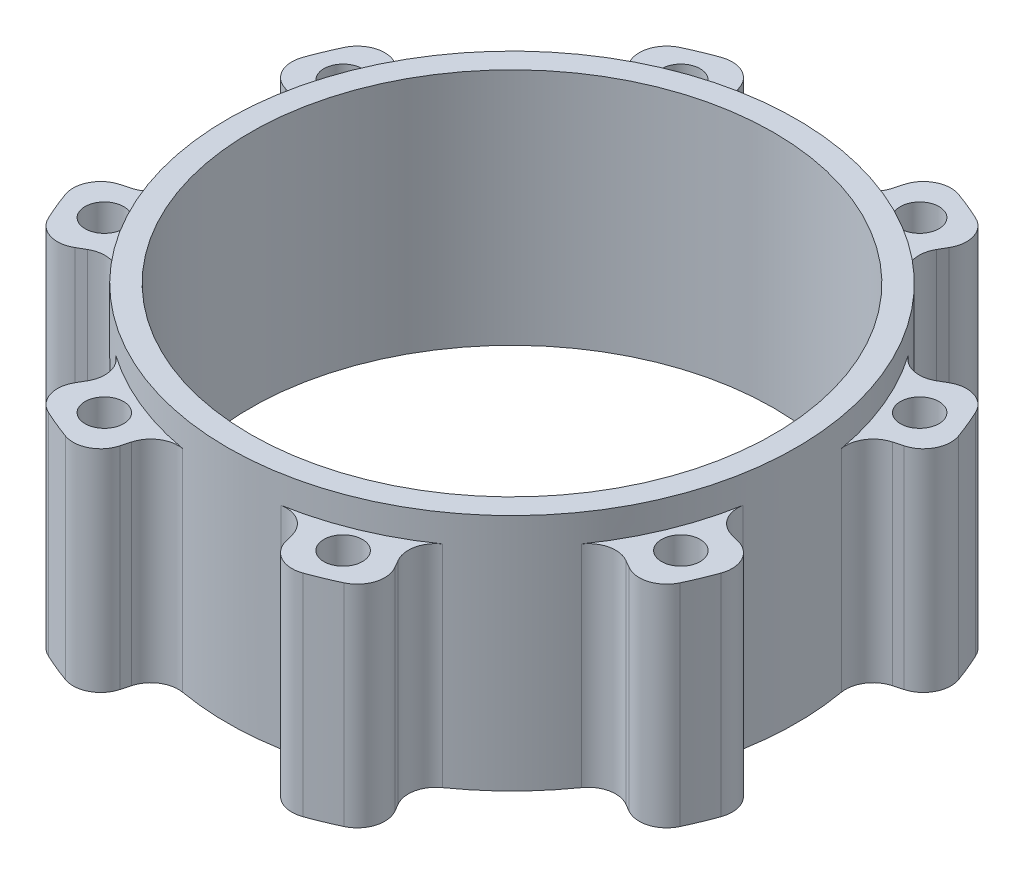
SolidWorks part; units mm, degrees
material "ABS"
ref_plane "前视基准面" through (0, 0, 0) normal (0, 0, 1) x (1, 0, 0)
ref_plane "上视基准面" through (0, 0, 0) normal (0, 1, 0) x (1, 0, 0)
ref_plane "右视基准面" through (0, 0, 0) normal (1, 0, 0) x (0, 0, -1)
other "Configuration Table"
sketch "草图1" plane through (0, 0, 0) normal (0, 1, 0) x (1, 0, 0)
  circle A0 centre (0, 0) radius 34 construction
  circle A1 centre (0, 0) radius 28.5
  circle A2 centre (0, 0) radius 38
  dimension "D1" = 68
  dimension "D2" = 4
  dimension "D3" = 57
extrude "凸台-拉伸1" add sketch "草图1" along normal blind 12
sketch "草图2" plane through (0, 12, 0) normal (0, 1, 0) x (1, 0, 0)
  line L0 (0, 0) -> (13.0112, 31.4119) construction
  circle A0 centre (0, 0) radius 34 construction
  circle A1 centre (13.0112, 31.4119) radius 2.1
  circle A2 centre (31.4119, 13.0112) radius 2.1
  circle A3 centre (31.4119, -13.0112) radius 2.1
  circle A4 centre (13.0112, -31.4119) radius 2.1
  circle A5 centre (-13.0112, -31.4119) radius 2.1
  circle A6 centre (-31.4119, -13.0112) radius 2.1
  circle A7 centre (-31.4119, 13.0112) radius 2.1
  circle A8 centre (-13.0112, 31.4119) radius 2.1
  dimension "D1" = 68
  dimension "D2" = 4.2
  dimension "D4" = 34
  dimension "D3" = 8
extrude "切除-拉伸1" cut sketch "草图2" against normal through all
sketch "草图4" plane through (0, 12, 0) normal (0, 1, 0) x (1, 0, 0)
  circle A0 centre (0, 0) radius 31
  circle A1 centre (0, 0) radius 28.5 construction
  circle A2 centre (0, 0) radius 28.5
  dimension "D1" = 62
extrude "凸台-拉伸2" add sketch "草图4" along normal blind 3
sketch "草图5" plane through (0, 0, 0) normal (0, -1, 0) x (1, 0, 0)
  line L0 (-9.8351, 36.7052) -> (0, 0)
  line L1 (0, 0) -> (9.8351, 36.7052)
  line L2 (0, 0) -> (0, 38) construction
  line L3 (0, 0) -> (32.909, 19)
  line L4 (19, 32.909) -> (0, 0)
  line L5 (0, 0) -> (36.7052, -9.8351)
  line L6 (36.7052, 9.8351) -> (0, 0)
  line L7 (0, 0) -> (19, -32.909)
  line L8 (32.909, -19) -> (0, 0)
  line L9 (0, 0) -> (-9.8351, -36.7052)
  line L10 (9.8351, -36.7052) -> (0, 0)
  line L11 (0, 0) -> (-32.909, -19)
  line L12 (-19, -32.909) -> (0, 0)
  line L13 (0, 0) -> (-36.7052, 9.8351)
  line L14 (-36.7052, -9.8351) -> (0, 0)
  line L15 (0, 0) -> (-19, 32.909)
  line L16 (-32.909, 19) -> (0, 0)
  circle A0 centre (0, 0) radius 31
  circle A1 centre (0, 0) radius 38 construction
  point P25 (0, 0)
  circle M12 centre (0, 0) radius 38
  dimension "D1" = 62
  dimension "D2" = 15
  dimension "D3" = 15
  dimension "D4" = 8
extrude "切除-拉伸2" cut sketch "草图5" against normal through all contours A0 L5 L6 M12 | A0 L3 L4 M12 | A0 L2 L0 M12 | L2 A0 L1 M12 | A0 L15 L16 M12 | A0 L13 L14 M12 | A0 L11 L12 M12 | A0 L9 L10 M12 | A0 L7 L8 M12 region at (-4.5057, 0, 34.2243) region at (4.5057, 0, 34.2243) region at (-24.2002, 0, 24.2002) region at (24.2002, 0, 24.2002) region at (34.2243, 0, 0) region at (24.2002, 0, -24.2002) region at (0, 0, -34.2243) region at (-24.2002, 0, -24.2002) region at (-34.2243, 0, 0)
fillet "圆角1" radius 3 32 edges at (15.5, 6, -26.8468) (19, 6, -32.909) (9.8351, 6, -36.7052) (8.0234, 6, -29.9437) (-8.0234, 6, -29.9437) (-9.8351, 6, -36.7052) (-19, 6, -32.909) (-15.5, 6, -26.8468) (-26.8468, 6, -15.5) (-32.909, 6, -19) (-36.7052, 6, -9.8351) (-29.9437, 6, -8.0234) (-29.9437, 6, 8.0234) (-36.7052, 6, 9.8351) (-32.909, 6, 19) (-26.8468, 6, 15.5) (-15.5, 6, 26.8468) (-19, 6, 32.909) (-9.8351, 6, 36.7052) (-8.0234, 6, 29.9437) (8.0234, 6, 29.9437) (9.8351, 6, 36.7052) (15.5, 6, 26.8468) (26.8468, 6, 15.5) (32.909, 6, 19) (36.7052, 6, 9.8351) (29.9437, 6, 8.0234) (29.9437, 6, -8.0234) (36.7052, 6, -9.8351) (32.909, 6, -19) (26.8468, 6, -15.5) (19, 6, 32.909)
sketch "草图6" plane through (0, 12, 0) normal (0, 1, 0) x (1, 0, 0)
  line L0 (-16.9337, -29.33) -> (-17.4356, -30.1993) construction
  line L1 (-9.0253, -33.683) -> (-8.7655, -32.7134) construction
  line L2 (-32.7134, -8.7655) -> (-33.683, -9.0253) construction
  line L3 (-30.1993, -17.4356) -> (-29.33, -16.9337) construction
  line L4 (-29.33, 16.9337) -> (-30.1993, 17.4356) construction
  line L5 (-33.683, 9.0253) -> (-32.7134, 8.7655) construction
  line L6 (-8.7655, 32.7134) -> (-9.0253, 33.683) construction
  line L7 (-17.4356, 30.1993) -> (-16.9337, 29.33) construction
  line L8 (16.9337, 29.33) -> (17.4356, 30.1993) construction
  line L9 (9.0253, 33.683) -> (8.7655, 32.7134) construction
  line L10 (32.7134, 8.7655) -> (33.683, 9.0253) construction
  line L11 (30.1993, 17.4356) -> (29.33, 16.9337) construction
  line L12 (8.7655, -32.7134) -> (9.0253, -33.683) construction
  line L13 (17.4356, -30.1993) -> (16.9337, -29.33) construction
  line L14 (29.33, -16.9337) -> (30.1993, -17.4356) construction
  line L15 (33.683, -9.0253) -> (32.7134, -8.7655) construction
  line L16 (-16.9337, -29.33) -> (-17.4356, -30.1993)
  line L17 (-9.0253, -33.683) -> (-8.7655, -32.7134)
  line L18 (-32.7134, -8.7655) -> (-33.683, -9.0253)
  line L19 (-30.1993, -17.4356) -> (-29.33, -16.9337)
  line L20 (-29.33, 16.9337) -> (-30.1993, 17.4356)
  line L21 (-33.683, 9.0253) -> (-32.7134, 8.7655)
  line L22 (-8.7655, 32.7134) -> (-9.0253, 33.683)
  line L23 (-17.4356, 30.1993) -> (-16.9337, 29.33)
  line L24 (16.9337, 29.33) -> (17.4356, 30.1993)
  line L25 (9.0253, 33.683) -> (8.7655, 32.7134)
  line L26 (32.7134, 8.7655) -> (33.683, 9.0253)
  line L27 (30.1993, 17.4356) -> (29.33, 16.9337)
  line L28 (8.7655, -32.7134) -> (9.0253, -33.683)
  line L29 (17.4356, -30.1993) -> (16.9337, -29.33)
  line L30 (29.33, -16.9337) -> (30.1993, -17.4356)
  line L31 (33.683, -9.0253) -> (32.7134, -8.7655)
  arc A0 (-17.4356, -30.1993) -> (-16.1093, -34.4164) centre (-14.8375, -31.6993) ccw construction
  arc A1 (-16.1093, -34.4164) -> (-12.9451, -35.7271) centre (0, 0) ccw construction
  arc A2 (-12.9451, -35.7271) -> (-9.0253, -33.683) centre (-11.9231, -32.9065) ccw construction
  arc A3 (-5.35, -30.5349) -> (-8.7655, -32.7134) centre (-5.8677, -33.4898) ccw construction
  arc A4 (-17.8084, -25.3744) -> (-5.35, -30.5349) centre (0, 0) ccw construction
  arc A5 (-16.9337, -29.33) -> (-17.8084, -25.3744) centre (-19.5318, -27.83) ccw construction
  arc A6 (-33.683, -9.0253) -> (-35.7271, -12.9451) centre (-32.9065, -11.9231) ccw construction
  arc A7 (-35.7271, -12.9451) -> (-34.4164, -16.1093) centre (0, 0) ccw construction
  arc A8 (-34.4164, -16.1093) -> (-30.1993, -17.4356) centre (-31.6993, -14.8375) ccw construction
  arc A9 (-25.3744, -17.8084) -> (-29.33, -16.9337) centre (-27.83, -19.5318) ccw construction
  arc A10 (-30.5349, -5.35) -> (-25.3744, -17.8084) centre (0, 0) ccw construction
  arc A11 (-32.7134, -8.7655) -> (-30.5349, -5.35) centre (-33.4898, -5.8677) ccw construction
  arc A12 (-30.1993, 17.4356) -> (-34.4164, 16.1093) centre (-31.6993, 14.8375) ccw construction
  arc A13 (-34.4164, 16.1093) -> (-35.7271, 12.9451) centre (0, 0) ccw construction
  arc A14 (-35.7271, 12.9451) -> (-33.683, 9.0253) centre (-32.9065, 11.9231) ccw construction
  arc A15 (-30.5349, 5.35) -> (-32.7134, 8.7655) centre (-33.4898, 5.8677) ccw construction
  arc A16 (-25.3744, 17.8084) -> (-30.5349, 5.35) centre (0, 0) ccw construction
  arc A17 (-29.33, 16.9337) -> (-25.3744, 17.8084) centre (-27.83, 19.5318) ccw construction
  arc A18 (-9.0253, 33.683) -> (-12.9451, 35.7271) centre (-11.9231, 32.9065) ccw construction
  arc A19 (-12.9451, 35.7271) -> (-16.1093, 34.4164) centre (0, 0) ccw construction
  arc A20 (-16.1093, 34.4164) -> (-17.4356, 30.1993) centre (-14.8375, 31.6993) ccw construction
  arc A21 (-17.8084, 25.3744) -> (-16.9337, 29.33) centre (-19.5318, 27.83) ccw construction
  arc A22 (-5.35, 30.5349) -> (-17.8084, 25.3744) centre (0, 0) ccw construction
  arc A23 (-8.7655, 32.7134) -> (-5.35, 30.5349) centre (-5.8677, 33.4898) ccw construction
  arc A24 (17.4356, 30.1993) -> (16.1093, 34.4164) centre (14.8375, 31.6993) ccw construction
  arc A25 (16.1093, 34.4164) -> (12.9451, 35.7271) centre (0, 0) ccw construction
  arc A26 (12.9451, 35.7271) -> (9.0253, 33.683) centre (11.9231, 32.9065) ccw construction
  arc A27 (5.35, 30.5349) -> (8.7655, 32.7134) centre (5.8677, 33.4898) ccw construction
  arc A28 (17.8084, 25.3744) -> (5.35, 30.5349) centre (0, 0) ccw construction
  arc A29 (16.9337, 29.33) -> (17.8084, 25.3744) centre (19.5318, 27.83) ccw construction
  arc A30 (33.683, 9.0253) -> (35.7271, 12.9451) centre (32.9065, 11.9231) ccw construction
  arc A31 (35.7271, 12.9451) -> (34.4164, 16.1093) centre (0, 0) ccw construction
  arc A32 (34.4164, 16.1093) -> (30.1993, 17.4356) centre (31.6993, 14.8375) ccw construction
  arc A33 (25.3744, 17.8084) -> (29.33, 16.9337) centre (27.83, 19.5318) ccw construction
  arc A34 (30.5349, 5.35) -> (25.3744, 17.8084) centre (0, 0) ccw construction
  arc A35 (32.7134, 8.7655) -> (30.5349, 5.35) centre (33.4898, 5.8677) ccw construction
  arc A36 (9.0253, -33.683) -> (12.9451, -35.7271) centre (11.9231, -32.9065) ccw construction
  arc A37 (12.9451, -35.7271) -> (16.1093, -34.4164) centre (0, 0) ccw construction
  arc A38 (16.1093, -34.4164) -> (17.4356, -30.1993) centre (14.8375, -31.6993) ccw construction
  arc A39 (17.8084, -25.3744) -> (16.9337, -29.33) centre (19.5318, -27.83) ccw construction
  arc A40 (5.35, -30.5349) -> (17.8084, -25.3744) centre (0, 0) ccw construction
  arc A41 (8.7655, -32.7134) -> (5.35, -30.5349) centre (5.8677, -33.4898) ccw construction
  arc A42 (30.1993, -17.4356) -> (34.4164, -16.1093) centre (31.6993, -14.8375) ccw construction
  arc A43 (34.4164, -16.1093) -> (35.7271, -12.9451) centre (0, 0) ccw construction
  arc A44 (35.7271, -12.9451) -> (33.683, -9.0253) centre (32.9065, -11.9231) ccw construction
  arc A45 (30.5349, -5.35) -> (32.7134, -8.7655) centre (33.4898, -5.8677) ccw construction
  arc A46 (25.3744, -17.8084) -> (30.5349, -5.35) centre (0, 0) ccw construction
  arc A47 (29.33, -16.9337) -> (25.3744, -17.8084) centre (27.83, -19.5318) ccw construction
  arc A48 (-17.4356, -30.1993) -> (-16.1093, -34.4164) centre (-14.8375, -31.6993) ccw
  arc A49 (-16.1093, -34.4164) -> (-12.9451, -35.7271) centre (0, 0) ccw
  arc A50 (-12.9451, -35.7271) -> (-9.0253, -33.683) centre (-11.9231, -32.9065) ccw
  arc A51 (-5.35, -30.5349) -> (-8.7655, -32.7134) centre (-5.8677, -33.4898) ccw
  arc A52 (-17.8084, -25.3744) -> (-5.35, -30.5349) centre (0, 0) ccw
  arc A53 (-16.9337, -29.33) -> (-17.8084, -25.3744) centre (-19.5318, -27.83) ccw
  arc A54 (-33.683, -9.0253) -> (-35.7271, -12.9451) centre (-32.9065, -11.9231) ccw
  arc A55 (-35.7271, -12.9451) -> (-34.4164, -16.1093) centre (0, 0) ccw
  arc A56 (-34.4164, -16.1093) -> (-30.1993, -17.4356) centre (-31.6993, -14.8375) ccw
  arc A57 (-25.3744, -17.8084) -> (-29.33, -16.9337) centre (-27.83, -19.5318) ccw
  arc A58 (-30.5349, -5.35) -> (-25.3744, -17.8084) centre (0, 0) ccw
  arc A59 (-32.7134, -8.7655) -> (-30.5349, -5.35) centre (-33.4898, -5.8677) ccw
  arc A60 (-30.1993, 17.4356) -> (-34.4164, 16.1093) centre (-31.6993, 14.8375) ccw
  arc A61 (-34.4164, 16.1093) -> (-35.7271, 12.9451) centre (0, 0) ccw
  arc A62 (-35.7271, 12.9451) -> (-33.683, 9.0253) centre (-32.9065, 11.9231) ccw
  arc A63 (-30.5349, 5.35) -> (-32.7134, 8.7655) centre (-33.4898, 5.8677) ccw
  arc A64 (-25.3744, 17.8084) -> (-30.5349, 5.35) centre (0, 0) ccw
  arc A65 (-29.33, 16.9337) -> (-25.3744, 17.8084) centre (-27.83, 19.5318) ccw
  arc A66 (-9.0253, 33.683) -> (-12.9451, 35.7271) centre (-11.9231, 32.9065) ccw
  arc A67 (-12.9451, 35.7271) -> (-16.1093, 34.4164) centre (0, 0) ccw
  arc A68 (-16.1093, 34.4164) -> (-17.4356, 30.1993) centre (-14.8375, 31.6993) ccw
  arc A69 (-17.8084, 25.3744) -> (-16.9337, 29.33) centre (-19.5318, 27.83) ccw
  arc A70 (-5.35, 30.5349) -> (-17.8084, 25.3744) centre (0, 0) ccw
  arc A71 (-8.7655, 32.7134) -> (-5.35, 30.5349) centre (-5.8677, 33.4898) ccw
  arc A72 (17.4356, 30.1993) -> (16.1093, 34.4164) centre (14.8375, 31.6993) ccw
  arc A73 (16.1093, 34.4164) -> (12.9451, 35.7271) centre (0, 0) ccw
  arc A74 (12.9451, 35.7271) -> (9.0253, 33.683) centre (11.9231, 32.9065) ccw
  arc A75 (5.35, 30.5349) -> (8.7655, 32.7134) centre (5.8677, 33.4898) ccw
  arc A76 (17.8084, 25.3744) -> (5.35, 30.5349) centre (0, 0) ccw
  arc A77 (16.9337, 29.33) -> (17.8084, 25.3744) centre (19.5318, 27.83) ccw
  arc A78 (33.683, 9.0253) -> (35.7271, 12.9451) centre (32.9065, 11.9231) ccw
  arc A79 (35.7271, 12.9451) -> (34.4164, 16.1093) centre (0, 0) ccw
  arc A80 (34.4164, 16.1093) -> (30.1993, 17.4356) centre (31.6993, 14.8375) ccw
  arc A81 (25.3744, 17.8084) -> (29.33, 16.9337) centre (27.83, 19.5318) ccw
  arc A82 (30.5349, 5.35) -> (25.3744, 17.8084) centre (0, 0) ccw
  arc A83 (32.7134, 8.7655) -> (30.5349, 5.35) centre (33.4898, 5.8677) ccw
  arc A84 (9.0253, -33.683) -> (12.9451, -35.7271) centre (11.9231, -32.9065) ccw
  arc A85 (12.9451, -35.7271) -> (16.1093, -34.4164) centre (0, 0) ccw
  arc A86 (16.1093, -34.4164) -> (17.4356, -30.1993) centre (14.8375, -31.6993) ccw
  arc A87 (17.8084, -25.3744) -> (16.9337, -29.33) centre (19.5318, -27.83) ccw
  arc A88 (5.35, -30.5349) -> (17.8084, -25.3744) centre (0, 0) ccw
  arc A89 (8.7655, -32.7134) -> (5.35, -30.5349) centre (5.8677, -33.4898) ccw
  arc A90 (30.1993, -17.4356) -> (34.4164, -16.1093) centre (31.6993, -14.8375) ccw
  arc A91 (34.4164, -16.1093) -> (35.7271, -12.9451) centre (0, 0) ccw
  arc A92 (35.7271, -12.9451) -> (33.683, -9.0253) centre (32.9065, -11.9231) ccw
  arc A93 (30.5349, -5.35) -> (32.7134, -8.7655) centre (33.4898, -5.8677) ccw
  arc A94 (25.3744, -17.8084) -> (30.5349, -5.35) centre (0, 0) ccw
  arc A95 (29.33, -16.9337) -> (25.3744, -17.8084) centre (27.83, -19.5318) ccw
extrude "凸台-拉伸3" add sketch "草图6" along normal blind 11
sketch "草图7" plane through (0, 15, 0) normal (0, 1, 0) x (1, 0, 0)
  circle A0 centre (0, 0) radius 28.5 construction
  circle A1 centre (0, 0) radius 28.5
  arc A16 (5.35, -30.5349) -> (17.8084, -25.3744) centre (0, 0) ccw
  arc A17 (17.8084, -25.3744) -> (25.3744, -17.8084) centre (0, 0) ccw
  arc A18 (25.3744, -17.8084) -> (30.5349, -5.35) centre (0, 0) ccw
  arc A19 (30.5349, -5.35) -> (30.5349, 5.35) centre (0, 0) ccw
  arc A20 (30.5349, 5.35) -> (25.3744, 17.8084) centre (0, 0) ccw
  arc A21 (25.3744, 17.8084) -> (17.8084, 25.3744) centre (0, 0) ccw
  arc A22 (17.8084, 25.3744) -> (5.35, 30.5349) centre (0, 0) ccw
  arc A23 (5.35, 30.5349) -> (-5.35, 30.5349) centre (0, 0) ccw
  arc A24 (-5.35, 30.5349) -> (-17.8084, 25.3744) centre (0, 0) ccw
  arc A25 (-17.8084, 25.3744) -> (-25.3744, 17.8084) centre (0, 0) ccw
  arc A26 (-25.3744, 17.8084) -> (-30.5349, 5.35) centre (0, 0) ccw
  arc A27 (-30.5349, 5.35) -> (-30.5349, -5.35) centre (0, 0) ccw
  arc A28 (-30.5349, -5.35) -> (-25.3744, -17.8084) centre (0, 0) ccw
  arc A29 (-25.3744, -17.8084) -> (-17.8084, -25.3744) centre (0, 0) ccw
  arc A30 (-17.8084, -25.3744) -> (-5.35, -30.5349) centre (0, 0) ccw
  arc A31 (-5.35, -30.5349) -> (5.35, -30.5349) centre (0, 0) ccw
  arc A32 (5.35, -30.5349) -> (17.8084, -25.3744) centre (0, 0) ccw
  arc A33 (17.8084, -25.3744) -> (25.3744, -17.8084) centre (0, 0) ccw
  arc A34 (25.3744, -17.8084) -> (30.5349, -5.35) centre (0, 0) ccw
  arc A35 (30.5349, -5.35) -> (30.5349, 5.35) centre (0, 0) ccw
  arc A36 (30.5349, 5.35) -> (25.3744, 17.8084) centre (0, 0) ccw
  arc A37 (25.3744, 17.8084) -> (17.8084, 25.3744) centre (0, 0) ccw
  arc A38 (17.8084, 25.3744) -> (5.35, 30.5349) centre (0, 0) ccw
  arc A39 (5.35, 30.5349) -> (-5.35, 30.5349) centre (0, 0) ccw
  arc A40 (-5.35, 30.5349) -> (-17.8084, 25.3744) centre (0, 0) ccw
  arc A41 (-17.8084, 25.3744) -> (-25.3744, 17.8084) centre (0, 0) ccw
  arc A42 (-25.3744, 17.8084) -> (-30.5349, 5.35) centre (0, 0) ccw
  arc A43 (-30.5349, 5.35) -> (-30.5349, -5.35) centre (0, 0) ccw
  arc A44 (-30.5349, -5.35) -> (-25.3744, -17.8084) centre (0, 0) ccw
  arc A45 (-25.3744, -17.8084) -> (-17.8084, -25.3744) centre (0, 0) ccw
  arc A46 (-17.8084, -25.3744) -> (-5.35, -30.5349) centre (0, 0) ccw
  arc A47 (-5.35, -30.5349) -> (5.35, -30.5349) centre (0, 0) ccw
  dimension "D1" = 0
extrude "凸台-拉伸4" add sketch "草图7" along normal blind 11
sketch "草图8" plane through (0, 0, 0) normal (0, -1, 0) x (1, 0, 0)
  line L16 (17.4356, -30.1993) -> (16.9337, -29.33)
  line L17 (29.33, -16.9337) -> (30.1993, -17.4356)
  line L18 (33.683, -9.0253) -> (32.7134, -8.7655)
  line L19 (32.7134, 8.7655) -> (33.683, 9.0253)
  line L20 (30.1993, 17.4356) -> (29.33, 16.9337)
  line L21 (16.9337, 29.33) -> (17.4356, 30.1993)
  line L22 (9.0253, 33.683) -> (8.7655, 32.7134)
  line L23 (-8.7655, 32.7134) -> (-9.0253, 33.683)
  line L24 (-17.4356, 30.1993) -> (-16.9337, 29.33)
  line L25 (-29.33, 16.9337) -> (-30.1993, 17.4356)
  line L26 (-33.683, 9.0253) -> (-32.7134, 8.7655)
  line L27 (-32.7134, -8.7655) -> (-33.683, -9.0253)
  line L28 (-30.1993, -17.4356) -> (-29.33, -16.9337)
  line L29 (-16.9337, -29.33) -> (-17.4356, -30.1993)
  line L30 (-9.0253, -33.683) -> (-8.7655, -32.7134)
  line L31 (8.7655, -32.7134) -> (9.0253, -33.683)
  line L32 (17.4356, -30.1993) -> (16.9337, -29.33)
  line L33 (29.33, -16.9337) -> (30.1993, -17.4356)
  line L34 (33.683, -9.0253) -> (32.7134, -8.7655)
  line L35 (32.7134, 8.7655) -> (33.683, 9.0253)
  line L36 (30.1993, 17.4356) -> (29.33, 16.9337)
  line L37 (16.9337, 29.33) -> (17.4356, 30.1993)
  line L38 (9.0253, 33.683) -> (8.7655, 32.7134)
  line L39 (-8.7655, 32.7134) -> (-9.0253, 33.683)
  line L40 (-17.4356, 30.1993) -> (-16.9337, 29.33)
  line L41 (-29.33, 16.9337) -> (-30.1993, 17.4356)
  line L42 (-33.683, 9.0253) -> (-32.7134, 8.7655)
  line L43 (-32.7134, -8.7655) -> (-33.683, -9.0253)
  line L44 (-30.1993, -17.4356) -> (-29.33, -16.9337)
  line L45 (-16.9337, -29.33) -> (-17.4356, -30.1993)
  line L46 (-9.0253, -33.683) -> (-8.7655, -32.7134)
  line L47 (8.7655, -32.7134) -> (9.0253, -33.683)
  circle A0 centre (13.0112, -31.4119) radius 2.1 construction
  circle A1 centre (-31.4119, 13.0112) radius 2.1
  circle A2 centre (-31.4119, 13.0112) radius 2.1
  circle A5 centre (31.4119, -13.0112) radius 2.1 construction
  circle A6 centre (31.4119, 13.0112) radius 2.1 construction
  circle A7 centre (13.0112, 31.4119) radius 2.1 construction
  circle A8 centre (-13.0112, 31.4119) radius 2.1 construction
  circle A9 centre (-31.4119, -13.0112) radius 2.1 construction
  circle A10 centre (-13.0112, -31.4119) radius 2.1 construction
  circle A11 centre (13.0112, -31.4119) radius 2.1
  circle A12 centre (31.4119, -13.0112) radius 2.1
  circle A13 centre (31.4119, 13.0112) radius 2.1
  circle A14 centre (13.0112, 31.4119) radius 2.1
  circle A15 centre (-13.0112, 31.4119) radius 2.1
  circle A16 centre (-31.4119, -13.0112) radius 2.1
  circle A17 centre (-13.0112, -31.4119) radius 2.1
  arc A48 (12.9451, -35.7271) -> (16.1093, -34.4164) centre (0, 0) ccw
  arc A49 (16.1093, -34.4164) -> (17.4356, -30.1993) centre (14.8375, -31.6993) ccw
  arc A50 (17.8084, -25.3744) -> (16.9337, -29.33) centre (19.5318, -27.83) ccw
  arc A51 (17.8084, -25.3744) -> (25.3744, -17.8084) centre (0, 0) ccw
  arc A52 (29.33, -16.9337) -> (25.3744, -17.8084) centre (27.83, -19.5318) ccw
  arc A53 (30.1993, -17.4356) -> (34.4164, -16.1093) centre (31.6993, -14.8375) ccw
  arc A54 (34.4164, -16.1093) -> (35.7271, -12.9451) centre (0, 0) ccw
  arc A55 (35.7271, -12.9451) -> (33.683, -9.0253) centre (32.9065, -11.9231) ccw
  arc A56 (30.5349, -5.35) -> (32.7134, -8.7655) centre (33.4898, -5.8677) ccw
  arc A57 (30.5349, -5.35) -> (30.5349, 5.35) centre (0, 0) ccw
  arc A58 (32.7134, 8.7655) -> (30.5349, 5.35) centre (33.4898, 5.8677) ccw
  arc A59 (33.683, 9.0253) -> (35.7271, 12.9451) centre (32.9065, 11.9231) ccw
  arc A60 (35.7271, 12.9451) -> (34.4164, 16.1093) centre (0, 0) ccw
  arc A61 (34.4164, 16.1093) -> (30.1993, 17.4356) centre (31.6993, 14.8375) ccw
  arc A62 (25.3744, 17.8084) -> (29.33, 16.9337) centre (27.83, 19.5318) ccw
  arc A63 (25.3744, 17.8084) -> (17.8084, 25.3744) centre (0, 0) ccw
  arc A64 (16.9337, 29.33) -> (17.8084, 25.3744) centre (19.5318, 27.83) ccw
  arc A65 (17.4356, 30.1993) -> (16.1093, 34.4164) centre (14.8375, 31.6993) ccw
  arc A66 (16.1093, 34.4164) -> (12.9451, 35.7271) centre (0, 0) ccw
  arc A67 (12.9451, 35.7271) -> (9.0253, 33.683) centre (11.9231, 32.9065) ccw
  arc A68 (5.35, 30.5349) -> (8.7655, 32.7134) centre (5.8677, 33.4898) ccw
  arc A69 (5.35, 30.5349) -> (-5.35, 30.5349) centre (0, 0) ccw
  arc A70 (-8.7655, 32.7134) -> (-5.35, 30.5349) centre (-5.8677, 33.4898) ccw
  arc A71 (-9.0253, 33.683) -> (-12.9451, 35.7271) centre (-11.9231, 32.9065) ccw
  arc A72 (-12.9451, 35.7271) -> (-16.1093, 34.4164) centre (0, 0) ccw
  arc A73 (-16.1093, 34.4164) -> (-17.4356, 30.1993) centre (-14.8375, 31.6993) ccw
  arc A74 (-17.8084, 25.3744) -> (-16.9337, 29.33) centre (-19.5318, 27.83) ccw
  arc A75 (-17.8084, 25.3744) -> (-25.3744, 17.8084) centre (0, 0) ccw
  arc A76 (-29.33, 16.9337) -> (-25.3744, 17.8084) centre (-27.83, 19.5318) ccw
  arc A77 (-30.1993, 17.4356) -> (-34.4164, 16.1093) centre (-31.6993, 14.8375) ccw
  arc A78 (-34.4164, 16.1093) -> (-35.7271, 12.9451) centre (0, 0) ccw
  arc A79 (-35.7271, 12.9451) -> (-33.683, 9.0253) centre (-32.9065, 11.9231) ccw
  arc A80 (-30.5349, 5.35) -> (-32.7134, 8.7655) centre (-33.4898, 5.8677) ccw
  arc A81 (-30.5349, 5.35) -> (-30.5349, -5.35) centre (0, 0) ccw
  arc A82 (-32.7134, -8.7655) -> (-30.5349, -5.35) centre (-33.4898, -5.8677) ccw
  arc A83 (-33.683, -9.0253) -> (-35.7271, -12.9451) centre (-32.9065, -11.9231) ccw
  arc A84 (-35.7271, -12.9451) -> (-34.4164, -16.1093) centre (0, 0) ccw
  arc A85 (-34.4164, -16.1093) -> (-30.1993, -17.4356) centre (-31.6993, -14.8375) ccw
  arc A86 (-25.3744, -17.8084) -> (-29.33, -16.9337) centre (-27.83, -19.5318) ccw
  arc A87 (-25.3744, -17.8084) -> (-17.8084, -25.3744) centre (0, 0) ccw
  arc A88 (-16.9337, -29.33) -> (-17.8084, -25.3744) centre (-19.5318, -27.83) ccw
  arc A89 (-17.4356, -30.1993) -> (-16.1093, -34.4164) centre (-14.8375, -31.6993) ccw
  arc A90 (-16.1093, -34.4164) -> (-12.9451, -35.7271) centre (0, 0) ccw
  arc A91 (-12.9451, -35.7271) -> (-9.0253, -33.683) centre (-11.9231, -32.9065) ccw
  arc A92 (-5.35, -30.5349) -> (-8.7655, -32.7134) centre (-5.8677, -33.4898) ccw
  arc A93 (-5.35, -30.5349) -> (5.35, -30.5349) centre (0, 0) ccw
  arc A94 (8.7655, -32.7134) -> (5.35, -30.5349) centre (5.8677, -33.4898) ccw
  arc A95 (9.0253, -33.683) -> (12.9451, -35.7271) centre (11.9231, -32.9065) ccw
  arc A96 (12.9451, -35.7271) -> (16.1093, -34.4164) centre (0, 0) ccw
  arc A97 (16.1093, -34.4164) -> (17.4356, -30.1993) centre (14.8375, -31.6993) ccw
  arc A98 (17.8084, -25.3744) -> (16.9337, -29.33) centre (19.5318, -27.83) ccw
  arc A99 (17.8084, -25.3744) -> (25.3744, -17.8084) centre (0, 0) ccw
  arc A100 (29.33, -16.9337) -> (25.3744, -17.8084) centre (27.83, -19.5318) ccw
  arc A101 (30.1993, -17.4356) -> (34.4164, -16.1093) centre (31.6993, -14.8375) ccw
  arc A102 (34.4164, -16.1093) -> (35.7271, -12.9451) centre (0, 0) ccw
  arc A103 (35.7271, -12.9451) -> (33.683, -9.0253) centre (32.9065, -11.9231) ccw
  arc A104 (30.5349, -5.35) -> (32.7134, -8.7655) centre (33.4898, -5.8677) ccw
  arc A105 (30.5349, -5.35) -> (30.5349, 5.35) centre (0, 0) ccw
  arc A106 (32.7134, 8.7655) -> (30.5349, 5.35) centre (33.4898, 5.8677) ccw
  arc A107 (33.683, 9.0253) -> (35.7271, 12.9451) centre (32.9065, 11.9231) ccw
  arc A108 (35.7271, 12.9451) -> (34.4164, 16.1093) centre (0, 0) ccw
  arc A109 (34.4164, 16.1093) -> (30.1993, 17.4356) centre (31.6993, 14.8375) ccw
  arc A110 (25.3744, 17.8084) -> (29.33, 16.9337) centre (27.83, 19.5318) ccw
  arc A111 (25.3744, 17.8084) -> (17.8084, 25.3744) centre (0, 0) ccw
  arc A112 (16.9337, 29.33) -> (17.8084, 25.3744) centre (19.5318, 27.83) ccw
  arc A113 (17.4356, 30.1993) -> (16.1093, 34.4164) centre (14.8375, 31.6993) ccw
  arc A114 (16.1093, 34.4164) -> (12.9451, 35.7271) centre (0, 0) ccw
  arc A115 (12.9451, 35.7271) -> (9.0253, 33.683) centre (11.9231, 32.9065) ccw
  arc A116 (5.35, 30.5349) -> (8.7655, 32.7134) centre (5.8677, 33.4898) ccw
  arc A117 (5.35, 30.5349) -> (-5.35, 30.5349) centre (0, 0) ccw
  arc A118 (-8.7655, 32.7134) -> (-5.35, 30.5349) centre (-5.8677, 33.4898) ccw
  arc A119 (-9.0253, 33.683) -> (-12.9451, 35.7271) centre (-11.9231, 32.9065) ccw
  arc A120 (-12.9451, 35.7271) -> (-16.1093, 34.4164) centre (0, 0) ccw
  arc A121 (-16.1093, 34.4164) -> (-17.4356, 30.1993) centre (-14.8375, 31.6993) ccw
  arc A122 (-17.8084, 25.3744) -> (-16.9337, 29.33) centre (-19.5318, 27.83) ccw
  arc A123 (-17.8084, 25.3744) -> (-25.3744, 17.8084) centre (0, 0) ccw
  arc A124 (-29.33, 16.9337) -> (-25.3744, 17.8084) centre (-27.83, 19.5318) ccw
  arc A125 (-30.1993, 17.4356) -> (-34.4164, 16.1093) centre (-31.6993, 14.8375) ccw
  arc A126 (-34.4164, 16.1093) -> (-35.7271, 12.9451) centre (0, 0) ccw
  arc A127 (-35.7271, 12.9451) -> (-33.683, 9.0253) centre (-32.9065, 11.9231) ccw
  arc A128 (-30.5349, 5.35) -> (-32.7134, 8.7655) centre (-33.4898, 5.8677) ccw
  arc A129 (-30.5349, 5.35) -> (-30.5349, -5.35) centre (0, 0) ccw
  arc A130 (-32.7134, -8.7655) -> (-30.5349, -5.35) centre (-33.4898, -5.8677) ccw
  arc A131 (-33.683, -9.0253) -> (-35.7271, -12.9451) centre (-32.9065, -11.9231) ccw
  arc A132 (-35.7271, -12.9451) -> (-34.4164, -16.1093) centre (0, 0) ccw
  arc A133 (-34.4164, -16.1093) -> (-30.1993, -17.4356) centre (-31.6993, -14.8375) ccw
  arc A134 (-25.3744, -17.8084) -> (-29.33, -16.9337) centre (-27.83, -19.5318) ccw
  arc A135 (-25.3744, -17.8084) -> (-17.8084, -25.3744) centre (0, 0) ccw
  arc A136 (-16.9337, -29.33) -> (-17.8084, -25.3744) centre (-19.5318, -27.83) ccw
  arc A137 (-17.4356, -30.1993) -> (-16.1093, -34.4164) centre (-14.8375, -31.6993) ccw
  arc A138 (-16.1093, -34.4164) -> (-12.9451, -35.7271) centre (0, 0) ccw
  arc A139 (-12.9451, -35.7271) -> (-9.0253, -33.683) centre (-11.9231, -32.9065) ccw
  arc A140 (-5.35, -30.5349) -> (-8.7655, -32.7134) centre (-5.8677, -33.4898) ccw
  arc A141 (-5.35, -30.5349) -> (5.35, -30.5349) centre (0, 0) ccw
  arc A142 (8.7655, -32.7134) -> (5.35, -30.5349) centre (5.8677, -33.4898) ccw
  arc A143 (9.0253, -33.683) -> (12.9451, -35.7271) centre (11.9231, -32.9065) ccw
  dimension "D1" = 0
  dimension "D2" = 0
extrude "切除-拉伸3" cut sketch "草图8" against normal through all contours A17 | A11 | A12 | A16 | A2 | A15 | A14 | A13 region at (-31.4119, 0, 13.0112) region at (13.0112, 0, -31.4119) region at (31.4119, 0, -13.0112) region at (13.0112, 0, 31.4119) region at (-13.0112, 0, 31.4119) region at (-31.4119, 0, -13.0112) region at (-13.0112, 0, -31.4119)
